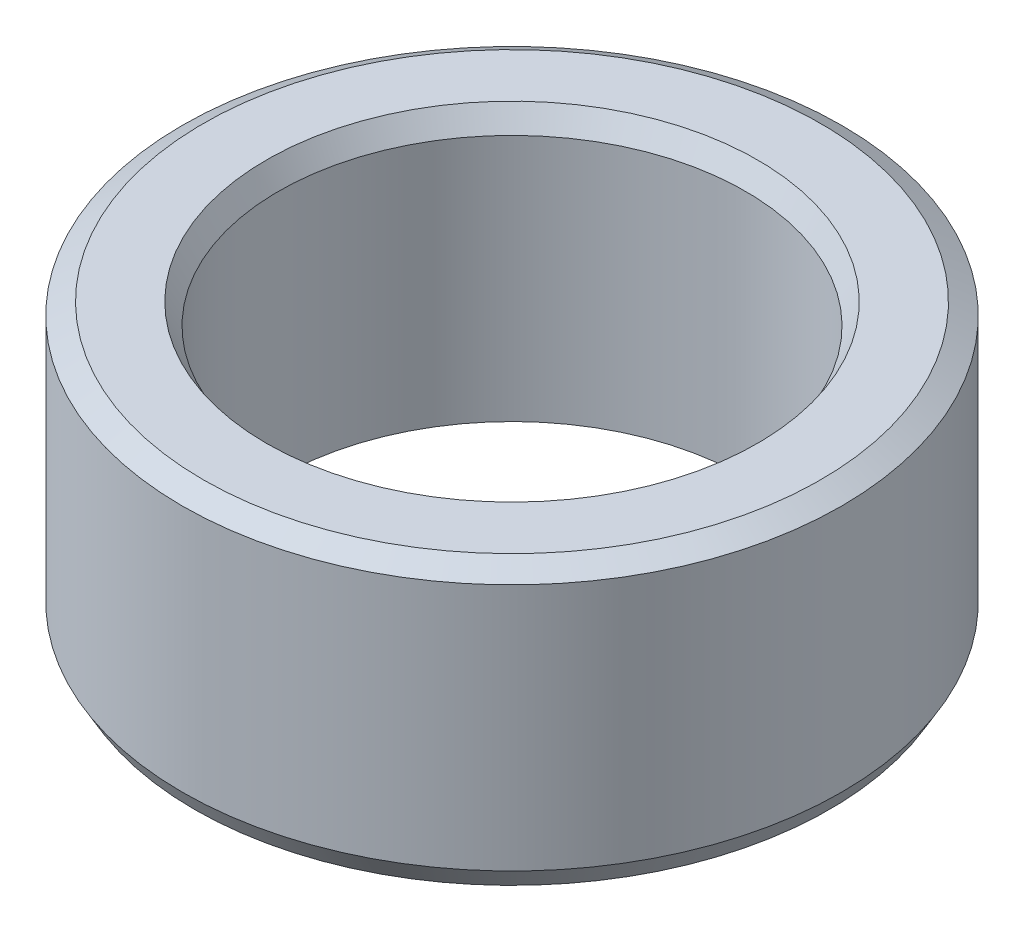
SolidWorks part; units mm, degrees
ref_plane "Front Plane" through (0, 0, 0) normal (0, 0, 1) x (1, 0, 0)
ref_plane "Top Plane" through (0, 0, 0) normal (0, 1, 0) x (1, 0, 0)
ref_plane "Right Plane" through (0, 0, 0) normal (1, 0, 0) x (0, 0, -1)
sketch "Sketch1" plane through (0, 0, 0) normal (0, 1, 0) x (1, 0, 0)
  circle A0 centre (0, 0) radius 30
  dimension "SLEEVE_OD" = 60
extrude "Boss-Extrude1" add sketch "Sketch1" along normal blind 25.5709
sketch "Sketch2" plane through (0, 0, 0) normal (0, 1, 0) x (1, 0, 0)
  circle A0 centre (0, 0) radius 21.2363
  dimension "BORE_D" = 42.4725
extrude "Cut-Extrude1" cut sketch "Sketch2" along normal through all
chamfer "Chamfer1" distance 1.1055 angle 60 4 edges at (0, 25.5709, 21.2363) (0, 0, 21.2363) (0, 0, 30) (0, 25.5709, 30) first distance on face at (0, 25.5709, 21.2363) first distance on face at (0, 0, 21.2363) first distance on face at (0, 25.5709, 30)
